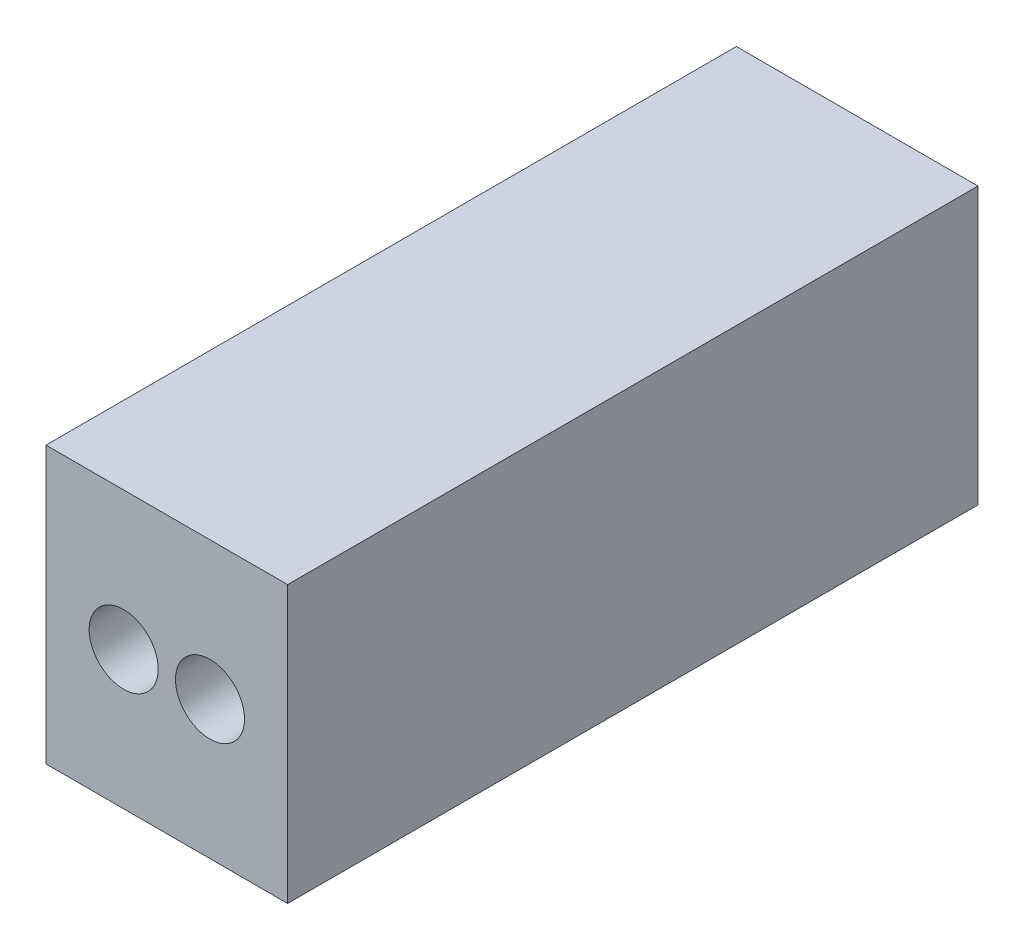
SolidWorks part; units mm, degrees
ref_plane "Front Plane" through (0, 0, 0) normal (0, 0, 1) x (1, 0, 0)
ref_plane "Top Plane" through (0, 0, 0) normal (0, 1, 0) x (1, 0, 0)
ref_plane "Right Plane" through (0, 0, 0) normal (1, 0, 0) x (0, 0, -1)
sketch "Sketch2" plane through (0, 0, 0) normal (0, 0, 1) x (1, 0, 0)
  line L1 (0, 0) -> (3.5, 0)
  line L2 (0, 0) -> (0, 4)
  line L3 (0, 4) -> (3.5, 4)
  line L4 (3.5, 0) -> (3.5, 4)
  dimension "D1" = 3.5
  dimension "D2" = 4
extrude "Boss-Extrude1" add sketch "Sketch2" along normal blind 10
sketch "Sketch3" plane through (0, 0, 10) normal (0, 0, 1) x (1, 0, 0)
  line L0 (0, 2) -> (3.5, 2) construction
  line L1 (0, 4) -> (0, 0) construction
  line L2 (3.5, 0) -> (3.5, 4) construction
  line L3 (0, 2) -> (3.5, 2) construction
  line L4 (3.5, 4) -> (0, 4) construction
  line L5 (0, 0) -> (3.5, 0) construction
  line L6 (1.125, 4) -> (1.125, 0) construction
  circle A0 centre (1.125, 2) radius 0.5
  circle A1 centre (2.375, 2) radius 0.5
  circle A21 centre (24.875, 2) radius 0.5 [skipped]
  circle A22 centre (23.625, 2) radius 0.5 [skipped]
  circle A23 centre (22.375, 2) radius 0.5 [skipped]
  circle A24 centre (21.125, 2) radius 0.5 [skipped]
  circle A25 centre (19.875, 2) radius 0.5 [skipped]
  circle A26 centre (18.625, 2) radius 0.5 [skipped]
  circle A27 centre (17.375, 2) radius 0.5 [skipped]
  circle A28 centre (16.125, 2) radius 0.5 [skipped]
  circle A29 centre (14.875, 2) radius 0.5 [skipped]
  circle A30 centre (13.625, 2) radius 0.5 [skipped]
  circle A31 centre (12.375, 2) radius 0.5 [skipped]
  circle A32 centre (11.125, 2) radius 0.5 [skipped]
  circle A33 centre (9.875, 2) radius 0.5 [skipped]
  circle A34 centre (7.375, 2) radius 0.5 [skipped]
  circle A35 centre (8.625, 2) radius 0.5 [skipped]
  circle A36 centre (3.625, 2) radius 0.5 [skipped]
  circle A37 centre (4.875, 2) radius 0.5 [skipped]
  circle A38 centre (6.125, 2) radius 0.5 [skipped]
  dimension "D1" = 1
  dimension "D2" = 2
  dimension "D3" = 1.125
  dimension "D5" = 1.25
  dimension "D4" = 20
extrude "Cut-Extrude1" cut sketch "Sketch3" against normal blind 5
sketch "Sketch4" plane through (0, 0, 10) normal (0, 0, 1) x (1, 0, 0)
  point P0 (1.125, 2)
  point P1 (2.375, 2)
other "CPoint1" parameters "Diameter"=25.4, "StubLength"=38.1
ref_axis "Axis1" through (1.125, 2, 20) along (0, 0, -1)
other "CPoint2" parameters "Diameter"=25.4, "StubLength"=38.1
ref_axis "Axis2" through (2.375, 2, 20) along (0, 0, -1)
